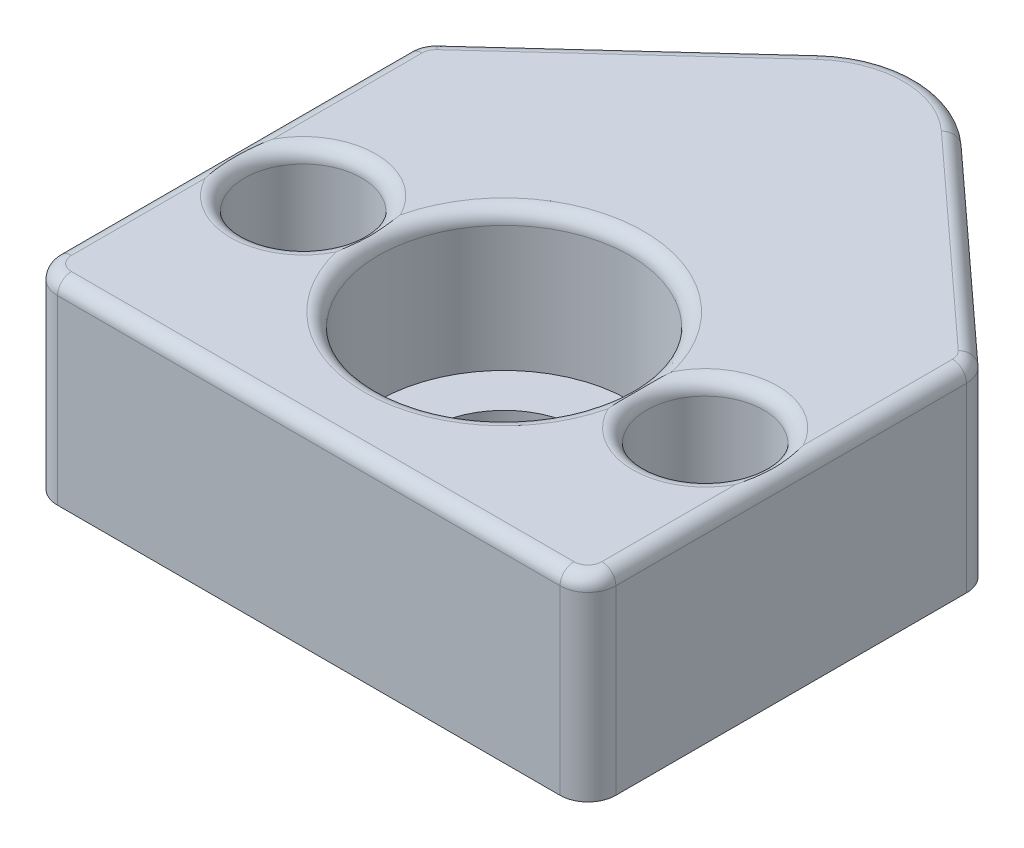
SolidWorks part; units mm, degrees
ref_plane "Спереди" through (0, 0, 0) normal (0, 0, 1) x (1, 0, 0)
ref_plane "Сверху" through (0, 0, 0) normal (0, 1, 0) x (1, 0, 0)
ref_plane "Справа" through (0, 0, 0) normal (1, 0, 0) x (0, 0, -1)
sketch "Эскиз1" plane through (0, 0, 0) normal (0, 1, 0) x (1, 0, 0)
  line L0 (0, -1000) -> (0, 49000) construction
  line L1 (-10, 7) -> (-2.5654, 13.8034)
  line L2 (-10, -7) -> (10, -7)
  line L3 (-10, -7) -> (-10, 7)
  line L4 (-10, 7) -> (10, 7)
  line L5 (10, -7) -> (10, 7)
  line L6 (-10, -7) -> (10, 7) construction
  line L7 (-10, 7) -> (10, -7) construction
  line L8 (10, 7) -> (2.5654, 13.8034)
  line L9 (-1.1124, 13.35) -> (1.1124, 13.35)
  line L11 (1.1124, 8.65) -> (-1.1124, 8.65)
  circle A0 centre (0, 0) radius 2.75
  circle A1 centre (0, 11) radius 2.6
  circle A2 centre (0, 11) radius 3.8
  dimension "D1" = 5.5
  dimension "D2" = 5.2
  dimension "D4" = 7.6
  dimension "D3" = 11
  dimension "D5" = 14
  dimension "D6" = 20
  dimension "D7" = 4.7
extrude "Бобышка-Вытянуть1" add sketch "Эскиз1" along normal blind 7 contours L2 L5 L4 L3 A0 | A2 L1 L4 L8 | A2 A1 | L9 A1 | L11 A1 region at (0, 0, -6.7559) region at (-6.1401, 0, -10.2458) region at (0, 0, -14.6925) region at (0, 0, -13.4504) region at (0, 0, -8.5496)
sketch "Эскиз2" plane through (0, 7, 0) normal (0, 1, 0) x (1, 0, 0)
  circle A0 centre (0, 0) radius 4.5
  circle A1 centre (0, 0) radius 2.75 construction
  circle A2 centre (0, 0) radius 2.75
  dimension "D1" = 9
extrude "Вырез-Вытянуть1" cut sketch "Эскиз2" against normal blind 5
sketch "Эскиз8" plane through (0, 7, 0) normal (0, 1, 0) x (1, 0, 0)
  line L0 (-1000, 0) -> (49000, 0) construction
  line L1 (0, -1000) -> (0, 49000) construction
  circle A0 centre (7.2, 0) radius 1.25
  circle A1 centre (-7.2, 0) radius 1.25
  dimension "D1" = 2.5
  dimension "D2" = 7.2
extrude "Вырез-Вытянуть3" cut sketch "Эскиз8" against normal through all contours A0 | A1 region at (7.2, 7, 0)
sketch "Эскиз9" plane through (0, 7, 0) normal (0, 1, 0) x (1, 0, 0)
  circle A0 centre (7.2, 0) radius 1.25 construction
  circle A1 centre (-7.2, 0) radius 1.25 construction
  circle A2 centre (7.2, 0) radius 1.25
  circle A3 centre (-7.2, 0) radius 1.25
  circle A4 centre (-7.2, 0) radius 2.1
  circle A5 centre (7.2, 0) radius 2.1
  dimension "D1" = 4.2
extrude "Вырез-Вытянуть4" cut sketch "Эскиз9" against normal blind 6
sketch "Эскиз10" plane through (0, 7, 0) normal (0, 1, 0) x (1, 0, 0)
  line L0 (1.1124, 8.65) -> (-1.1124, 8.65) construction
  line L1 (1.1124, 8.65) -> (-1.1124, 8.65)
  line L2 (-1.1124, 13.35) -> (1.1124, 13.35) construction
  line L3 (-1.1124, 13.35) -> (1.1124, 13.35)
  line L5 (-10, -7) -> (10, -7)
  line L6 (10, -7) -> (10, 7)
  line L7 (10, 7) -> (2.5654, 13.8034)
  line L8 (-2.5654, 13.8034) -> (-10, 7)
  line L9 (-10, 7) -> (-10, -7)
  line L10 (-10, -7) -> (10, -7)
  line L11 (10, -7) -> (10, 7)
  line L12 (10, 7) -> (2.5654, 13.8034)
  line L13 (-2.5654, 13.8034) -> (-10, 7)
  line L14 (-10, 7) -> (-10, -7)
  arc A0 (1.1124, 8.65) -> (1.1124, 13.35) centre (0, 11) ccw construction
  arc A1 (2.5654, 13.8034) -> (-2.5654, 13.8034) centre (0, 11) ccw
  arc A2 (2.5654, 13.8034) -> (-2.5654, 13.8034) centre (0, 11) ccw
  arc A3 (1.1124, 8.65) -> (1.1124, 13.35) centre (0, 11) ccw
  arc A4 (-1.1124, 13.35) -> (-1.1124, 8.65) centre (0, 11) ccw construction
  arc A5 (-1.1124, 13.35) -> (-1.1124, 8.65) centre (0, 11) ccw
  arc M20 (1.1124, 13.35) -> (1.1124, 8.65) centre (0, 11) cw
  line M21 (1.1124, 8.65) -> (-1.1124, 8.65)
  arc M22 (-1.1124, 8.65) -> (-1.1124, 13.35) centre (0, 11) cw
  line M23 (-1.1124, 13.35) -> (1.1124, 13.35)
  dimension "D1" = 0
extrude "Бобышка-Вытянуть2" add sketch "Эскиз10" against normal blind 4 contours M20 M23 M22 M21 region at (0, 7, -11)
sketch "Эскиз11" plane through (0, 3, 0) normal (0, -1, 0) x (1, 0, 0)
  line L0 (0, -1000) -> (0, 49000) construction
  line L1 (1.1124, -8.65) -> (-1.1124, -8.65) construction
  line L2 (-0.75, -8.65) -> (0.75, -8.65)
  line L3 (-0.75, -8.65) -> (-0.75, -13.35)
  line L4 (-0.75, -13.35) -> (0.75, -13.35)
  line L5 (0.75, -8.65) -> (0.75, -13.35)
  line L6 (-1.1124, -13.35) -> (1.1124, -13.35) construction
  dimension "D1" = 1.5
extrude "Бобышка-Вытянуть3" add sketch "Эскиз11" along normal blind 1
sketch "Эскиз12" plane through (0, 0, 0) normal (0, -1, 0) x (1, 0, 0)
  line L0 (0, -1000) -> (0, 49000) construction
  line L1 (-2, -8.65) -> (-2, -9.3387)
  line L2 (-2, -5.5) -> (2, -5.5)
  line L3 (-2, -5.5) -> (-2, -8.65)
  line L4 (-2, -8.65) -> (2, -8.65)
  line L5 (2, -5.5) -> (2, -8.65)
  line L6 (-2, -5.5) -> (2, -8.65) construction
  line L7 (-2, -8.65) -> (2, -5.5) construction
  line L8 (2, -8.65) -> (2, -9.3387)
  line L12 (10, 7) -> (-10, 7)
  line L13 (-10, 7) -> (-10, -7)
  line L14 (-10, -7) -> (-2.5654, -13.8034)
  line L15 (2.5654, -13.8034) -> (10, -7)
  line L16 (10, -7) -> (10, 7)
  line L17 (10, 7) -> (-10, 7)
  line L18 (-10, 7) -> (-10, -7)
  line L19 (-10, -7) -> (-2.5654, -13.8034)
  line L20 (2.5654, -13.8034) -> (10, -7)
  line L21 (10, -7) -> (10, 7)
  arc A1 (-1.1124, -8.65) -> (-1.1124, -13.35) centre (0, -11) ccw construction
  arc A2 (-2.5654, -13.8034) -> (2.5654, -13.8034) centre (0, -11) ccw
  arc A3 (-2.5654, -13.8034) -> (2.5654, -13.8034) centre (0, -11) ccw
  arc A4 (1.1124, -13.35) -> (1.1124, -8.65) centre (0, -11) ccw construction
  point P0 (0, -7.075)
  arc M12 (1.1124, -8.65) -> (1.1124, -13.35) centre (0, -11) cw
  arc M14 (-1.1124, -13.35) -> (-1.1124, -8.65) centre (0, -11) cw
  line M15 (-1.1124, -8.65) -> (1.1124, -8.65)
  dimension "D1" = 5.5
  dimension "D2" = 0
  dimension "D3" = 4
extrude "Вырез-Вытянуть5" cut sketch "Эскиз12" against normal blind 2 contours L5 L2 L3 L4 M15 | L4 L1 M14 | L8 L4 M12 region at (-1.7277, 0, -8.8626) region at (0, 0, -7.075) region at (1.7277, 0, -8.8626)
sketch "Эскиз13" plane through (0, 2, 0) normal (0, -1, 0) x (1, 0, 0)
  line L0 (-0.75, -8.65) -> (-0.75, -5.5)
  line L1 (-2, -5.5) -> (2, -5.5) construction
  line L2 (0.75, -8.65) -> (0.75, -5.5)
  line L3 (-2, -5.5) -> (2, -5.5) construction
  line L12 (-0.75, -8.65) -> (-0.75, -13.35)
  line L13 (-0.75, -13.35) -> (0.75, -13.35)
  line L14 (0.75, -13.35) -> (0.75, -8.65)
  line L15 (0.75, -8.65) -> (1.1124, -8.65)
  line L16 (2, -9.3387) -> (2, -5.5)
  line L17 (2, -5.5) -> (-2, -5.5)
  line L18 (-2, -5.5) -> (-2, -9.3387)
  line L19 (-1.1124, -8.65) -> (-0.75, -8.65)
  line L20 (-0.75, -8.65) -> (-0.75, -13.35)
  line L21 (-0.75, -13.35) -> (0.75, -13.35)
  line L22 (0.75, -13.35) -> (0.75, -8.65)
  line L23 (0.75, -8.65) -> (1.1124, -8.65)
  line L24 (2, -9.3387) -> (2, -5.5)
  line L25 (2, -5.5) -> (-2, -5.5)
  line L26 (-2, -5.5) -> (-2, -9.3387)
  line L27 (-1.1124, -8.65) -> (-0.75, -8.65)
  arc A2 (2, -9.3387) -> (1.1124, -8.65) centre (0, -11) ccw
  arc A3 (-1.1124, -8.65) -> (-2, -9.3387) centre (0, -11) ccw
  arc A4 (2, -9.3387) -> (1.1124, -8.65) centre (0, -11) ccw
  arc A5 (-1.1124, -8.65) -> (-2, -9.3387) centre (0, -11) ccw
  line M14 (0.75, -8.65) -> (1.1124, -8.65)
  arc M15 (1.1124, -8.65) -> (2, -9.3387) centre (0, -11) cw
  line M16 (2, -9.3387) -> (2, -5.5)
  line M17 (2, -5.5) -> (-2, -5.5)
  line M18 (-2, -5.5) -> (-2, -9.3387)
  arc M19 (-2, -9.3387) -> (-1.1124, -8.65) centre (0, -11) cw
  line M20 (-1.1124, -8.65) -> (-0.75, -8.65)
  dimension "D1" = 0
extrude "Вырез-Вытянуть6" cut sketch "Эскиз13" against normal blind 1 contours L2 M14 M15 M16 M17 | L0 M20 M17 M18 M19 region at (-1.3968, 2, -7.1855) region at (1.3968, 2, -7.1855)
fillet "Скругление1" radius 1 4 edges at (-10, 3.5, -7) (-10, 3.5, 7) (10, 3.5, 7) (10, 3.5, -7)
fillet "Скругление2" radius 0.5 13 edges at (0, 7, -14.8) (6.1202, 7, -10.5504) (9.9152, 7, -6.9626) (10, 7, -0.2798) (9.7071, 7, 6.7071) (0, 7, 7) (-9.7071, 7, 6.7071) (-10, 7, -0.2798) (-9.9152, 7, -6.9626) (-6.1202, 7, -10.5504) (0, 7, 4.5) (7.2, 7, 2.1) (-7.2, 7, 2.1)
